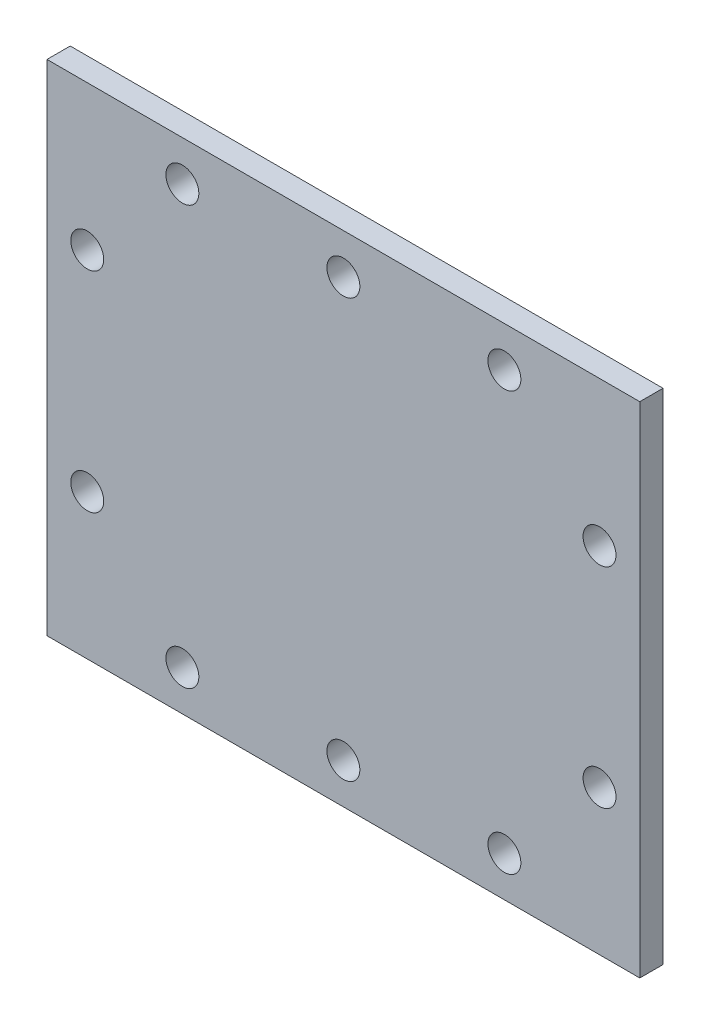
SolidWorks part; units mm, degrees
other "Title Block Table1"
other "DetailItem18"
other "DetailItem19"
other "DetailItem22"
material "PC High Viscosity"
ref_plane "Top Plane" through (0, 0, 0) normal (0, 0, 1) x (1, 0, 0)
ref_plane "Right Plane" through (0, 0, 0) normal (0, 1, 0) x (1, 0, 0)
ref_plane "Front Plane" through (0, 0, 0) normal (1, 0, 0) x (0, 0, -1)
sketch "Sketch1" plane through (0, 0, 0) normal (0, 0, 1) x (1, 0, 0)
  line L1 (0, 0) -> (81, 0)
  line L2 (0, 0) -> (0, 68.2)
  line L3 (0, 68.2) -> (81, 68.2)
  line L4 (81, 0) -> (81, 68.2)
  dimension "D1" = 81
  dimension "D2" = 68.2
extrude "Window, Polycarbonate" add sketch "Sketch1" along normal blind 3.175
hole_wizard "10X, Clearance Hole, M4" positions "Sketch2" profile "Sketch3" hole size "M4" standard "ANSI Metric" end condition through all
sketch "Sketch2" plane through (0, 0, 3.175) normal (0, 0, 1) x (1, 0, 0)
  line L1 (5.5, 62.7) -> (75.5, 62.7) construction
  line L2 (5.5, 62.7) -> (5.5, 5.5) construction
  line L3 (5.5, 5.5) -> (75.5, 5.5) construction
  line L4 (75.5, 62.7) -> (75.5, 5.5) construction
  line L5 (81, 0) -> (81, 68.2) construction
  line L7 (5.5, 34.1) -> (75.5, 34.1) construction
  line L8 (81, 68.2) -> (0, 68.2) construction
  circle A0 centre (18.5, 62.7) radius 5.5 construction
  circle A1 centre (18.5, 5.5) radius 5.5 construction
  circle A2 centre (5.5, 48.4) radius 5.5 construction
  circle A3 centre (75.5, 48.4) radius 5.5 construction
  point P0 (40.5, 5.5)
  point P2 (62.5, 5.5)
  point P4 (18.5, 5.5)
  point P6 (5.5, 19.8)
  point P8 (5.5, 48.4)
  point P10 (18.5, 62.7)
  point P12 (62.5, 62.7)
  point P14 (75.5, 48.4)
  point P16 (75.5, 19.8)
  point P118 (75.5, 34.1)
  point P121 (81, 34.1)
  point P144 (-14.097, 58.7175)
  point P146 (40.5, 62.7)
  point P148 (-22.0975, 69.695)
  point P154 (40.5, 62.7)
  point P156 (40.5, 5.5)
  point P174 (40.5, 68.2)
  dimension "D3" = 11
  dimension "D1" = 57.2
  dimension "D2" = 70
  dimension "D4" = 22
  dimension "D5" = 22
  dimension "D6" = 28.6
  dimension "D7" = 14.3
sketch "Sketch3" plane through (40.5, 5.5, 3.175) normal (1, 0, 0) x (0, -1, 0)
  line L0 (0, 0) -> (0, 3.175)
  line L1 (0, 3.175) -> (2.25, 3.175)
  line L2 (2.25, 3.175) -> (2.25, 0)
  line L5 (2.25, 0) -> (0, 0)
  line L11 (0, -6.35) -> (0, 107.95) construction
  dimension "Thru Hole Dia." = 4.5
  dimension "Thru Hole Depth" = 3.175
equation "\"D5@Sketch2\"=\"D4@Sketch2\""
equation "\"D7@Sketch2\"=\"D6@Sketch2\"/2"
